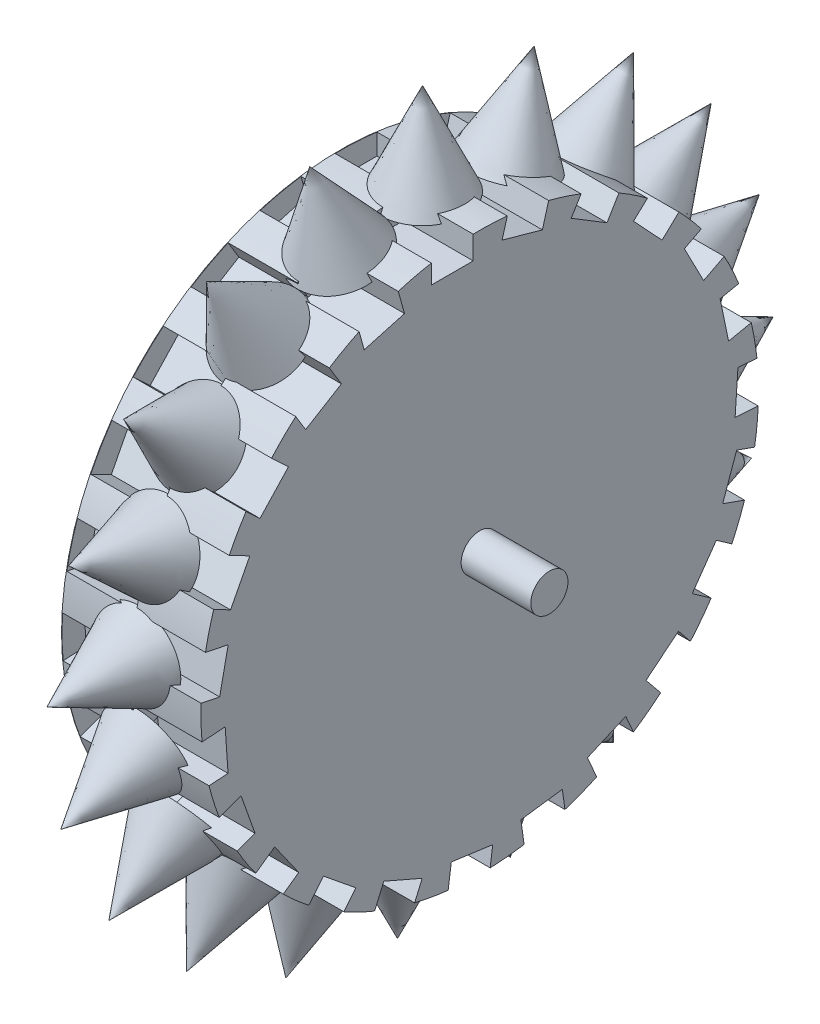
SolidWorks part; units mm, degrees
material "Nylon 101"
ref_plane "Front Plane" through (0, 0, 0) normal (0, 0, 1) x (1, 0, 0)
ref_plane "Top Plane" through (0, 0, 0) normal (0, 1, 0) x (1, 0, 0)
ref_plane "Right Plane" through (0, 0, 0) normal (1, 0, 0) x (0, 0, -1)
sketch "Sketch1" plane through (0, 0, 0) normal (1, 0, 0) x (0, 0, -1)
  circle A0 centre (0, 0) radius 60
  circle A1 centre (0, 0) radius 10
  dimension "D1" = 120
  dimension "D2" = 20
extrude "Boss-Extrude1" add sketch "Sketch1" along normal blind 20 and the other way blind 20 contours A0
sketch "Sketch2" plane through (20, 0, 0) normal (1, 0, 0) x (0, 0, -1)
  circle A0 centre (0, 0) radius 60
  dimension "D1" = 120
sketch "Sketch3" plane through (-20, 0, 0) normal (-1, 0, 0) x (0, 0, 1)
  circle A0 centre (0, 0) radius 60
  dimension "D1" = 120
extrude "Cut-Extrude1" cut sketch "Sketch2" against normal blind 5 contours A0
extrude "Cut-Extrude2" cut sketch "Sketch3" against normal blind 5 contours A0
sketch "Sketch4" plane through (-15, 0, 0) normal (-1, 0, 0) x (0, 0, 1)
  circle A0 centre (0, 0) radius 4
  dimension "D1" = 8
sketch "Sketch5" plane through (15, 0, 0) normal (1, 0, 0) x (0, 0, -1)
  circle A0 centre (0, 0) radius 10
  dimension "D1" = 20
extrude "Cut-Extrude3" cut sketch "Sketch4" against normal blind 33 contours A0
ref_plane "Plane1" through (0, 60, 0) normal (0, 1, 0) x (1, 0, 0)
sketch "Sketch10" plane through (0, 60, 0) normal (0, 1, 0) x (1, 0, 0)
  line L0 (15, -1.3952) -> (15, -10.3952)
  line L3 (-14.8878, -1.2271) -> (-14.8878, 7.7729)
  line L4 (-14.8878, 7.7729) -> (0.1122, 7.7729)
  line L5 (0.1122, 7.7729) -> (0.1122, -1.2271)
  line L6 (0.1122, -1.2271) -> (-14.8878, -1.2271)
  line L9 (15, -1.3952) -> (0, -1.3952)
  line L10 (0, -1.3952) -> (0, -10.3952)
  line L11 (0, -10.3952) -> (15, -10.3952)
  dimension "D1" = 9
  dimension "D2" = 9
  dimension "D3" = 15
  dimension "D4" = 15
extrude "Cut-Extrude13" cut sketch "Sketch10" against normal blind 5 contours L10 L11 L0 L9 | L4 L5 L6 L3 region at (7.5, 60, 5.8952)
pattern_circular "CirPattern1" count 23 over 360 about axis through (18, 0, 0) along (-1, 0, 0) of "Cut-Extrude13"
sketch "Sketch16" plane through (0, 0, 0) normal (1, 0, 0) x (0, 0, -1)
  line L0 (78.1539, -2.7015) -> (58.4458, 6.4217)
  line L1 (55.5812, 6.6176) -> (59.6643, 6.3383) construction
  line L2 (58.4458, 6.4217) -> (59.9392, -2.7015)
  line L3 (59.9392, -2.7015) -> (78.1539, -2.7015)
  line L4 (54.967, -2.3614) -> (59.9392, -2.7015) construction
  line L5 (54.967, -2.3614) -> (59.9392, -2.7015) construction
  arc A0 (59.9392, -2.7015) -> (59.8315, 4.4942) centre (0, 0) ccw construction
revolve "Revolve2" add sketch "Sketch16" angle 360 about L3
pattern_circular "CirPattern29" count 20 over 360 about axis through (-20, 0, 0) along (1, 0, 0) of "Revolve2" reverse direction yes
sketch "Sketch17" plane through (0, 0, 0) normal (1, 0, 0) x (0, 0, -1)
  circle A0 centre (0, 0) radius 4
extrude "Boss-Extrude2" add sketch "Sketch17" along normal blind 30
scale "Scale3" scale about centroid uniform scaling yes scale factor 1.2
